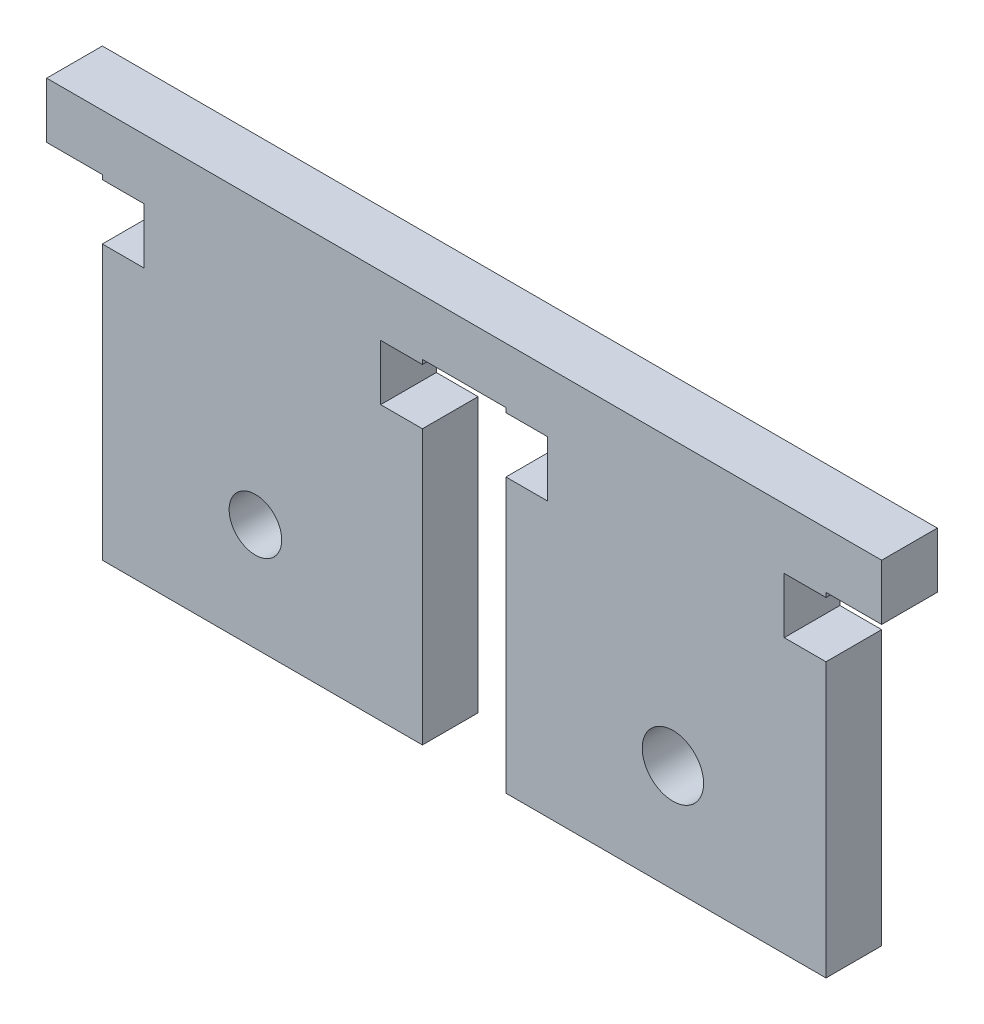
SolidWorks part; units mm, degrees
material "AISI 4130 Steel, annealed at 865C"
ref_plane "X-Y Datum" through (0, 0, 0) normal (0, 0, 1) x (1, 0, 0)
ref_plane "X-Z Datum" through (0, 0, 0) normal (0, 1, 0) x (1, 0, 0)
ref_plane "Y-Z Datum" through (0, 0, 0) normal (1, 0, 0) x (0, 0, -1)
sketch "Sketch3" plane through (0, 0, 0) normal (0, 0, 1) x (1, 0, 0)
  line L1 (-47.625, -30.48) -> (47.625, -30.48)
  line L2 (-47.625, -30.48) -> (-47.625, 30.48)
  line L3 (-47.625, 30.48) -> (47.625, 30.48)
  line L4 (47.625, -30.48) -> (47.625, 30.48)
  line L5 (-47.625, -30.48) -> (47.625, 30.48) construction
  line L6 (-47.625, 30.48) -> (47.625, -30.48) construction
  point P0 (0, 0)
  dimension "D1" = 95.25
  dimension "D2" = 60.96
extrude "Boss-Extrude1" add sketch "Sketch3" along normal blind 6.35
sketch "Sketch4" plane through (0, 0, 6.35) normal (0, 0, 1) x (1, 0, 0)
  line L0 (-47.625, 15.24) -> (-41.275, 15.24)
  line L1 (-47.625, 30.48) -> (-47.625, -30.48) construction
  line L2 (-41.275, 15.24) -> (-4.7625, 15.24)
  line L3 (-4.7625, 15.24) -> (4.7625, 15.24)
  line L4 (4.7625, 15.24) -> (41.275, 15.24)
  line L5 (41.275, 15.24) -> (47.625, 15.24)
  line L6 (47.625, -30.48) -> (47.625, 30.48) construction
  line L7 (0, 15.24) -> (0, -30.48) construction
  line L8 (-41.275, 15.24) -> (-47.625, 15.24)
  line L9 (-41.275, 15.24) -> (-41.275, -30.48)
  line L10 (-41.275, -30.48) -> (-47.625, -30.48)
  line L11 (-47.625, 15.24) -> (-47.625, -30.48)
  line L12 (-47.625, -30.48) -> (47.625, -30.48) construction
  line L13 (-1.5875, -16.0071) -> (1.5875, -16.0071)
  line L14 (-1.5875, -16.0071) -> (-1.5875, 0.7671)
  line L17 (-4.7625, 15.24) -> (4.7625, 15.24)
  line L19 (-4.7625, -30.48) -> (4.7625, -30.48)
  line L20 (-4.7625, -30.48) -> (-4.7625, 15.24)
  line L25 (-4.7625, 15.24) -> (4.7625, 15.24)
  line L26 (4.7625, -30.48) -> (4.7625, 15.24)
  line L27 (41.275, 15.24) -> (47.625, 15.24)
  line L28 (41.275, 15.24) -> (41.275, -30.48)
  line L29 (41.275, -30.48) -> (47.625, -30.48)
  line L31 (-4.7625, -30.48) -> (4.7625, 15.24) construction
  line L32 (-4.7625, 15.24) -> (4.7625, -30.48) construction
  line L33 (-1.5875, 0.7671) -> (1.5875, 0.7671)
  line L34 (1.5875, -16.0071) -> (1.5875, 0.7671)
  line L35 (-1.5875, -16.0071) -> (1.5875, 0.7671) construction
  line L36 (-1.5875, 0.7671) -> (1.5875, -16.0071) construction
  point P15 (0, -7.62)
  point P20 (0, -7.62)
  line M5 (47.625, -30.48) -> (47.625, 30.48)
  line M7 (-47.625, 30.48) -> (-47.625, -30.48)
  line M8 (-47.625, -30.48) -> (47.625, -30.48)
  dimension "D1" = 6.35
  dimension "D2" = 36.5125
  dimension "D3" = 6.35
  dimension "D4" = 36.5125
  dimension "D5" = 9.525
  dimension "D6" = 45.72
  dimension "D7" = 3.175
  dimension "D8" = 42.8625
  dimension "D9" = 45.72
extrude "Cut-Extrude1" cut sketch "Sketch4" against normal blind 6.35 contours L9 L0 M7 M8 | L3 M8 | L5 L28 M8 M5 | L13 L34 L33 L14 region at (-44.45, -7.62, 6.35) region at (0, 14.773, 6.35) region at (44.45, -7.62, 6.35) region at (0, -7.62, 6.35)
sketch "Sketch5" plane through (0, 0, 6.35) normal (0, 0, 1) x (1, 0, 0)
  line L9 (-23.0188, -30.48) -> (-23.0188, 30.48) construction
  line L10 (-41.275, 8.382) -> (-36.5125, 8.382)
  line L11 (-41.275, 8.382) -> (-41.275, 14.732)
  line L12 (-41.275, 14.732) -> (-36.5125, 14.732)
  line L13 (-36.5125, 8.382) -> (-36.5125, 14.732)
  line L14 (-41.275, -30.48) -> (-4.7625, -30.48) construction
  line L15 (47.625, 30.48) -> (-47.625, 30.48) construction
  line L16 (-41.275, 14.732) -> (-47.6562, 14.732)
  line L17 (-4.7625, 8.382) -> (-9.525, 8.382)
  line L18 (-4.7625, 8.382) -> (-4.7625, 14.732)
  line L19 (-4.7625, 14.732) -> (-9.525, 14.732)
  line L20 (-9.525, 8.382) -> (-9.525, 14.732)
  line L21 (-41.275, 14.732) -> (-41.275, 8.382)
  line L22 (-41.275, 8.382) -> (-47.6562, 8.382)
  line L23 (-47.6562, 14.732) -> (-47.6562, 8.382)
  line M5 (-41.275, 15.24) -> (-41.275, -30.48)
  line M15 (-47.625, 30.48) -> (-47.625, 15.24)
  line M16 (-47.625, 15.24) -> (-41.275, 15.24)
  dimension "D1" = 6.35
  dimension "D2" = 4.7625
  dimension "D3" = 15.748
extrude "Cut-Extrude2" cut sketch "Sketch5" against normal blind 6.35 contours L10 L13 L12 L11 | L20 L17 L18 L19 | L16 L23 L22 M5 M16 M15 region at (-38.8938, 11.557, 6.35) region at (-44.4656, 11.557, 6.35) region at (-7.1437, 11.557, 6.35)
mirror "Mirror1" about plane through (0, 0, 0) normal (1, 0, 0) of "Cut-Extrude2"
sketch "Sketch8" [suppressed] plane through (0, 15.24, 0) normal (0, -1, 0) x (1, 0, 0)
  line L0 (-9.525, 3.175) -> (9.525, 3.175) construction
  line L1 (-9.525, 0) -> (-9.525, 6.35) construction
  line L2 (9.525, 0) -> (9.525, 6.35) construction
  line L3 (-4.7625, 6.35) -> (4.7625, 6.35) construction
  line L4 (-4.7625, 0) -> (4.7625, 0)
  line L5 (-4.7625, 0) -> (-4.7625, 6.35)
  line L6 (-4.7625, 6.35) -> (4.7625, 6.35)
  line L7 (4.7625, 0) -> (4.7625, 6.35)
  line L8 (-4.7625, 0) -> (4.7625, 6.35) construction
  line L9 (-4.7625, 6.35) -> (4.7625, 0) construction
  point P6 (0, 3.175)
  line M3 (-4.7625, 0) -> (4.7625, 0)
  dimension "D1" = 4.7625
extrude "Cut-Extrude3" [suppressed] cut sketch "Sketch8" against normal blind 1.5875 contours L7 L0 L5 M3
sketch "Sketch9" plane through (0, 30.48, 0) normal (0, 1, 0) x (1, 0, 0)
  line L1 (-47.625, 0) -> (47.625, 0)
  line L2 (-47.625, 0) -> (-47.625, -6.35)
  line L3 (-47.625, -6.35) -> (47.625, -6.35)
  line L4 (47.625, 0) -> (47.625, -6.35)
extrude "Cut-Extrude6" cut sketch "Sketch9" against normal blind 8.89
sketch "Sketch10" plane through (0, 0, 6.35) normal (0, 0, 1) x (1, 0, 0)
  circle A0 centre (-23.8125, -10.6279) radius 3 construction
  circle A1 centre (23.8138, -10.6279) radius 3.5 construction
  circle A2 centre (-23.8125, -10.6279) radius 3
  circle A3 centre (23.8138, -10.6279) radius 3.5
extrude "Cut-Extrude7" cut sketch "Sketch10" against normal blind 6.35
sketch "Sketch11" plane through (0, -30.48, 0) normal (0, -1, 0) x (1, 0, 0)
  line L1 (-41.275, 6.35) -> (41.275, 6.35)
  line L2 (-41.275, 6.35) -> (-41.275, 0)
  line L3 (-41.275, 0) -> (41.275, 0)
  line L4 (41.275, 6.35) -> (41.275, 0)
extrude "Cut-Extrude9" cut sketch "Sketch11" against normal blind 7.62
